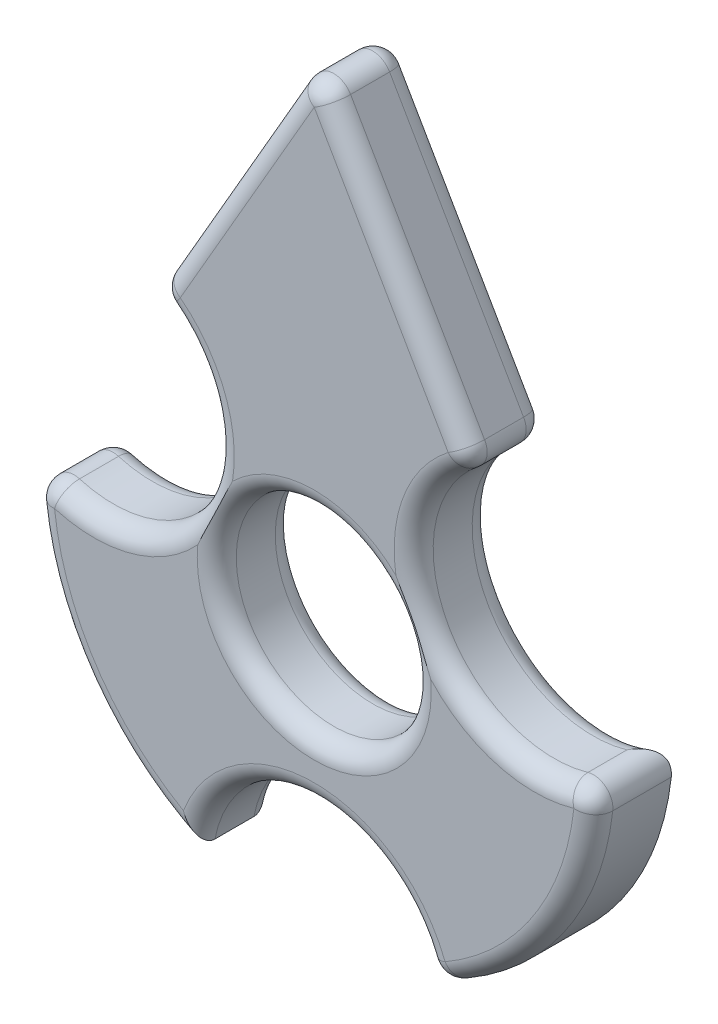
SolidWorks part; units mm, degrees
ref_plane "Front Plane" through (0, 0, 0) normal (0, 0, 1) x (1, 0, 0)
ref_plane "Top Plane" through (0, 0, 0) normal (0, 1, 0) x (1, 0, 0)
ref_plane "Right Plane" through (0, 0, 0) normal (1, 0, 0) x (0, 0, -1)
sketch "Sketch1" plane through (0, 0, 0) normal (0, 0, 1) x (1, 0, 0)
  line L0 (0, 0) -> (42860.4054, 0) construction
  line L1 (0, -1144) -> (0, -72) construction
  line L2 (0, 125) -> (41, 53.9859)
  line L3 (0, 125) -> (-41, 53.9859)
  line L4 (0, -40) -> (0, 42860.4054) construction
  circle A0 centre (0, 0) radius 25
  arc A1 (30.4601, -65.2394) -> (71.9994, 0.292) centre (0, 0) ccw
  arc A2 (30.4601, -65.2394) -> (-30.4601, -65.2394) centre (0, -71) ccw
  arc A3 (41, 53.9859) -> (71.9994, 0.292) centre (56.5, 27.1391) ccw
  arc A5 (-41, 53.9859) -> (-71.9994, 0.292) centre (-56.5, 27.1391) cw
  arc A7 (-71.9994, 0.292) -> (-30.4601, -65.2394) centre (0, 0) ccw
  point P14 (0, 0)
  point P17 (0, 0)
  point P18 (0, 0)
  point P19 (0, 0)
  point P20 (41.7081, 52.7595)
  point P24 (41, 55.306)
  dimension "D1" = 50
  dimension "D2" = 144
  dimension "D5" = 62
  dimension "D6" = 62
  dimension "D3" = 60
  dimension "D4" = 125
  dimension "D7" = 196
  dimension "D8" = 113
extrude "Boss-Extrude1" add sketch "Sketch1" along normal blind 20
fillet "Fillet2" radius 5 21 edges at (25, 0, 0) (25, 0, 20) (-20.5, 89.493, 0) (-29.653, 11.6394, 0) (-60.8118, -38.5477, 0) (0, -40, 0) (29.653, 11.6394, 0) (20.5, 89.493, 0) (-20.5, 89.493, 20) (-29.653, 11.6394, 20) (-60.8118, -38.5477, 20) (0, -40, 20) (60.8118, -38.5477, 20) (29.653, 11.6394, 20) (20.5, 89.493, 20) (0, 125, 10) (41, 53.9859, 10) (71.9994, 0.292, 10) (30.4601, -65.2394, 10) (-71.9994, 0.292, 10) (-41, 53.9859, 10)
